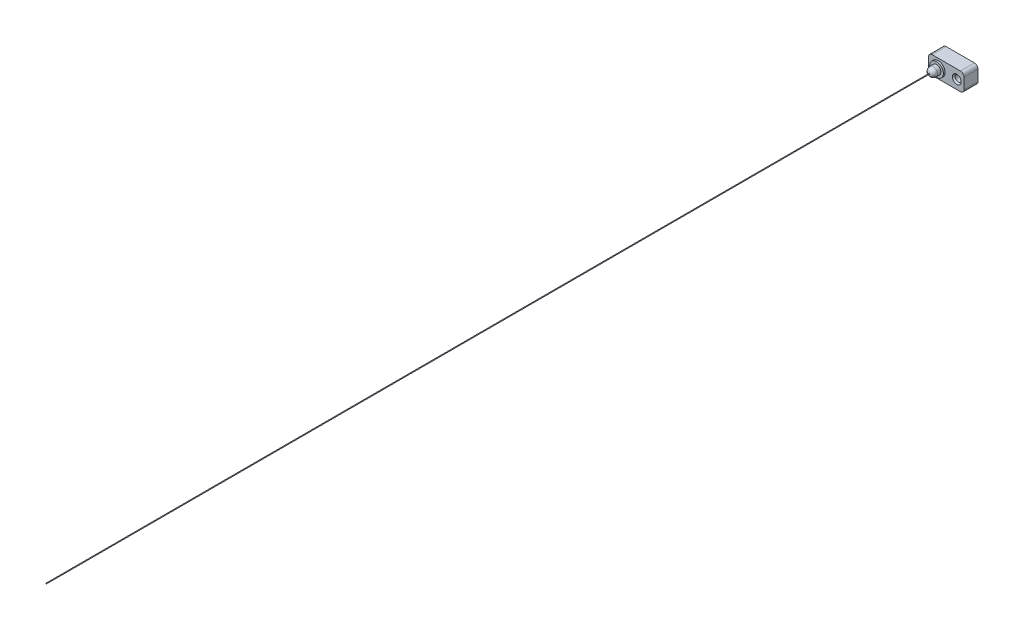
SolidWorks part; units mm, degrees
ref_plane "Front" through (0, 0, 0) normal (0, 0, 1) x (1, 0, 0)
ref_plane "Top" through (0, 0, 0) normal (0, 1, 0) x (1, 0, 0)
ref_plane "Right" through (0, 0, 0) normal (1, 0, 0) x (0, 0, -1)
sketch "Sketch1" plane through (0, 0, 0) normal (0, 0, 1) x (1, 0, 0)
  line L1 (0, 0) -> (20.066, 0)
  line L2 (0, 0) -> (0, 10.16)
  line L3 (0, 10.16) -> (20.066, 10.16)
  line L4 (20.066, 0) -> (20.066, 10.16)
  dimension "D1" = 20.066
  dimension "D2" = 10.16
extrude "Boss-Extrude1" add sketch "Sketch1" along normal blind 7.9502
sketch "Sketch2" plane through (0, 0, 7.9502) normal (0, 0, 1) x (1, 0, 0)
  line L0 (0, 10.16) -> (0, 0) construction
  line L1 (5.5, 10.16) -> (5.5, 0) construction
  line L2 (20.066, 10.16) -> (0, 10.16) construction
  line L3 (0, 0) -> (20.066, 0) construction
  circle A0 centre (5.5, 5.08) radius 3.8862
  dimension "D1" = 7.7724
  dimension "D2" = 5.5
extrude "Boss-Extrude2" add sketch "Sketch2" along normal blind 0.9906
sketch "Sketch3" plane through (0, 0, 8.9408) normal (0, 0, 1) x (1, 0, 0)
  circle A0 centre (5.5, 5.08) radius 2.4765
  dimension "D1" = 4.953
extrude "Boss-Extrude3" add sketch "Sketch3" along normal blind 4.2164
hole_wizard "CSK for M3 SFHCS1" positions "Sketch4" profile "Sketch5" countersink size "M3" standard "ANSI Metric" end condition through all
sketch "Sketch4" plane through (0, 0, 7.9502) normal (0, 0, 1) x (1, 0, 0)
  line L0 (16, 10.16) -> (16, 0) construction
  line L1 (20.066, 10.16) -> (0, 10.16) construction
  line L2 (0, 0) -> (20.066, 0) construction
  circle A0 centre (5.5, 5.08) radius 2.4765 construction
  point P0 (16, 5.08)
  dimension "D1" = 10.5
sketch "Sketch5" plane through (16, 5.08, 7.9502) normal (1, 0, 0) x (0, -1, 0)
  line L0 (0, 0) -> (0, 7.9502)
  line L1 (0, 7.9502) -> (1.7, 7.9502)
  line L2 (1.7, 7.9502) -> (1.7, 0.8)
  line L3 (1.7, 0.8) -> (2.5, 0)
  line L5 (2.5, 0) -> (0, 0)
  line L6 (-1.7, 0.8) -> (-2.5, 0) construction
  line L11 (0, -6.35) -> (0, 107.95) construction
  dimension "Thru Hole Dia." = 3.4
  dimension "Thru Hole Depth" = 7.9502
  dimension "Near C'Sink Dia." = 5
  dimension "Near C'Sink Angle" = 90
fillet "Fillet1" radius 2.286 1 edges at (7.9765, 5.08, 13.1572)
fillet "Fillet2" radius 2 4 edges at (0, 0, 3.9751) (0, 10.16, 3.9751) (20.066, 0, 3.9751) (20.066, 10.16, 3.9751)
ref_plane "Plane1" [suppressed] through (0, 5.08, 0) normal (0, 1, 0) x (1, 0, 0)
sketch "Sketch7" [suppressed] plane through (0, 5.08, 0) normal (0, 1, 0) x (1, 0, 0)
  line L0 (7.9765, -10.8712) -> (94.8006, -503.2751)
  line L1 (5.5, -13.1572) -> (5.5, -14.3589) construction
  line L2 (5.3095, -13.1572) -> (5.6905, -13.1572) construction
  line L3 (94.8006, -503.2751) -> (94.73, -503.2751)
  line L4 (94.73, -503.2751) -> (7.9059, -10.8712)
  line L5 (7.9059, -10.8712) -> (7.9765, -10.8712)
  line L6 (7.9765, -10.8712) -> (3.0235, -10.8712) construction
  arc A1 (5.6905, -13.1572) -> (7.9765, -10.8712) centre (5.6905, -10.8712) ccw construction
  dimension "D1" = 10
  dimension "D2" = 500
  dimension "D3" = 0.0706
revolve "Revolve1" [suppressed] add sketch "Sketch7" angle 360 about L1
sketch "Sketch8" plane through (0, 0, 13.1572) normal (0, 0, 1) x (1, 0, 0)
  circle A0 centre (5.5, 5.08) radius 0.1905 construction
  circle A1 centre (5.5, 5.08) radius 0.1905
extrude "Boss-Extrude4" add sketch "Sketch8" along normal blind 500 separate body
